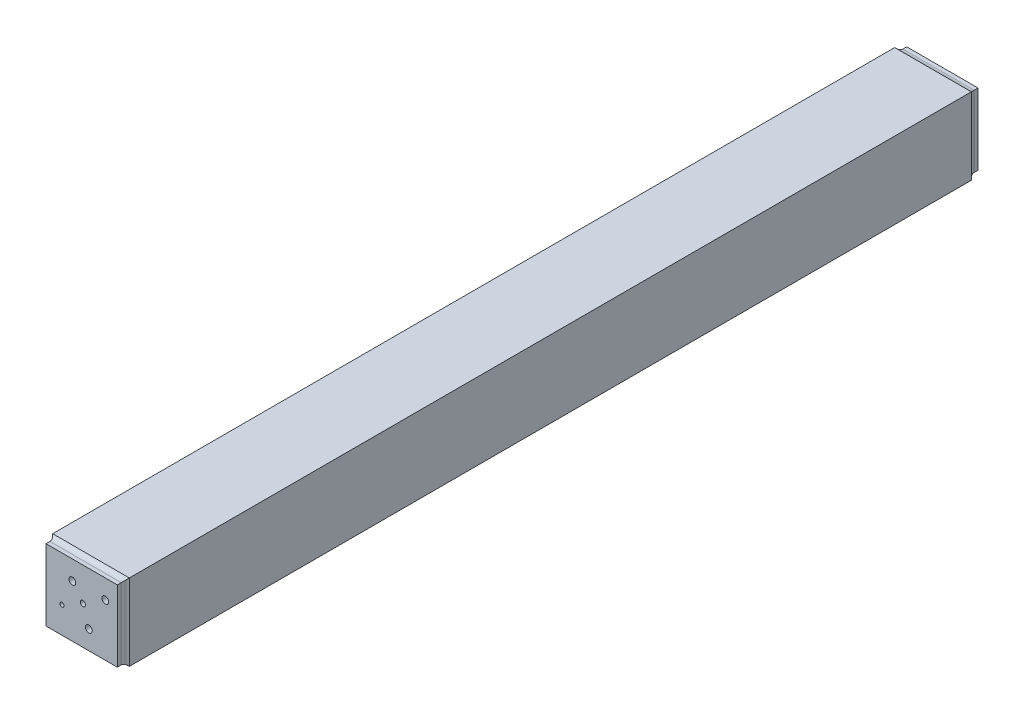
SolidWorks part; units mm, degrees
material "1060 Alloy"
ref_plane "Front Plane" through (0, 0, 0) normal (0, 0, 1) x (1, 0, 0)
ref_plane "Top Plane" through (0, 0, 0) normal (0, 1, 0) x (1, 0, 0)
ref_plane "Right Plane" through (0, 0, 0) normal (1, 0, 0) x (0, 0, -1)
sketch "Sketch1" plane through (0, 0, 0) normal (0, 0, 1) x (1, 0, 0)
  line L0 (22.265, 0) -> (22.265, -44.53) construction
  line L1 (0, 0) -> (44.53, 0) construction
  line L2 (0, 0) -> (0, -44.53) construction
  line L3 (0, -44.53) -> (44.53, -44.53) construction
  line L4 (44.53, 0) -> (44.53, -44.53) construction
  line L5 (42.98, -1.55) -> (1.55, -1.55)
  line L6 (42.98, -1.55) -> (42.98, -42.98)
  line L7 (42.98, -42.98) -> (1.55, -42.98)
  line L8 (1.55, -1.55) -> (1.55, -42.98)
  line L9 (44.53, -22.265) -> (0, -22.265) construction
  line L10 (31.93, -10.9) -> (31.93, 0) construction
  line L11 (31.93, -12.9) -> (12.93, -12.9) construction
  line L12 (33.93, -12.9) -> (44.53, -12.9) construction
  circle A0 centre (12.93, -12.9) radius 2
  circle A1 centre (31.93, -12.9) radius 2
  circle A2 centre (12.93, -12.9) radius 2.6 construction
  dimension "D2" = 4
  dimension "D1" = 44.53
  dimension "D3" = 41.43
  dimension "D4" = 10.9
  dimension "D5" = 10.6
extrude "Boss-Extrude1" add sketch "Sketch1" against normal blind 5.42
sketch "Sketch2" plane through (0, 0, 0) normal (0, 0, -1) x (-1, 0, 0)
  line L0 (0, 0) -> (-44.53, 0) construction
  line L1 (-3.175, -3.175) -> (-41.355, -3.175)
  line L2 (-3.175, -3.175) -> (-3.175, -41.355)
  line L3 (-3.175, -41.355) -> (-41.355, -41.355)
  line L4 (-41.355, -3.175) -> (-41.355, -41.355)
  line L5 (0, 0) -> (-44.53, 0)
  line L6 (0, 0) -> (0, -44.53)
  line L7 (0, -44.53) -> (-44.53, -44.53)
  line L8 (-44.53, 0) -> (-44.53, -44.53)
  line L9 (0, -44.53) -> (-44.53, -44.53) construction
  line L10 (-44.53, 0) -> (-44.53, -44.53) construction
  line L11 (0, 0) -> (0, -44.53) construction
  line L13 (-22.265, -41.355) -> (-22.265, -44.53) construction
  line L14 (-41.355, -22.265) -> (-44.53, -22.265) construction
  line L15 (-22.265, -3.175) -> (-22.265, 0) construction
  line L16 (-3.175, -22.265) -> (0, -22.265) construction
  dimension "D1" = 3.175
extrude "Boss-Extrude2" add sketch "Sketch2" against normal blind 489.16
sketch "Sketch3" plane through (0, 0, 489.16) normal (0, 0, 1) x (1, 0, 0)
  line L0 (22.265, -1.55) -> (22.265, -42.98) construction
  line L1 (1.55, -1.55) -> (42.98, -1.55)
  line L2 (1.55, -1.55) -> (1.55, -42.98)
  line L3 (1.55, -42.98) -> (42.98, -42.98)
  line L4 (42.98, -1.55) -> (42.98, -42.98)
  line L5 (1.55, -22.265) -> (42.98, -22.265) construction
  line L6 (22.265, 0) -> (22.265, -44.53) construction
  line L7 (44.53, -22.265) -> (0, -22.265) construction
  line L8 (42.98, -1.55) -> (1.55, -1.55) construction
  circle A0 centre (16.84, -12.6755) radius 2
  circle A1 centre (36.01, -12.6755) radius 2
  circle A2 centre (26.425, -32.01) radius 2
  circle A3 centre (22.9728, -20.927) radius 1.505
  circle A4 centre (10.8715, -27.5658) radius 1.2
  circle A5 centre (31.93, -12.9) radius 2 construction
  circle A6 centre (36.01, -12.6755) radius 4.5 construction
  circle A7 centre (16.84, -12.6755) radius 4.5 construction
  circle A8 centre (26.425, -32.01) radius 4.5 construction
  dimension "D1" = 3.01
  dimension "D2" = 2.4
extrude "Boss-Extrude3" add sketch "Sketch3" along normal blind 5.42
fillet "Fillet1" radius 4 8 edges at (22.265, -42.98, 489.16) (42.98, -22.265, 489.16) (1.55, -22.265, 489.16) (22.265, -1.55, 489.16) (1.55, -22.265, 0) (22.265, -42.98, 0) (42.98, -22.265, 0) (22.265, -1.55, 0)
ref_axis "Axis1" through (31.93, -12.9, -5.42) along (0, 0, 1)
